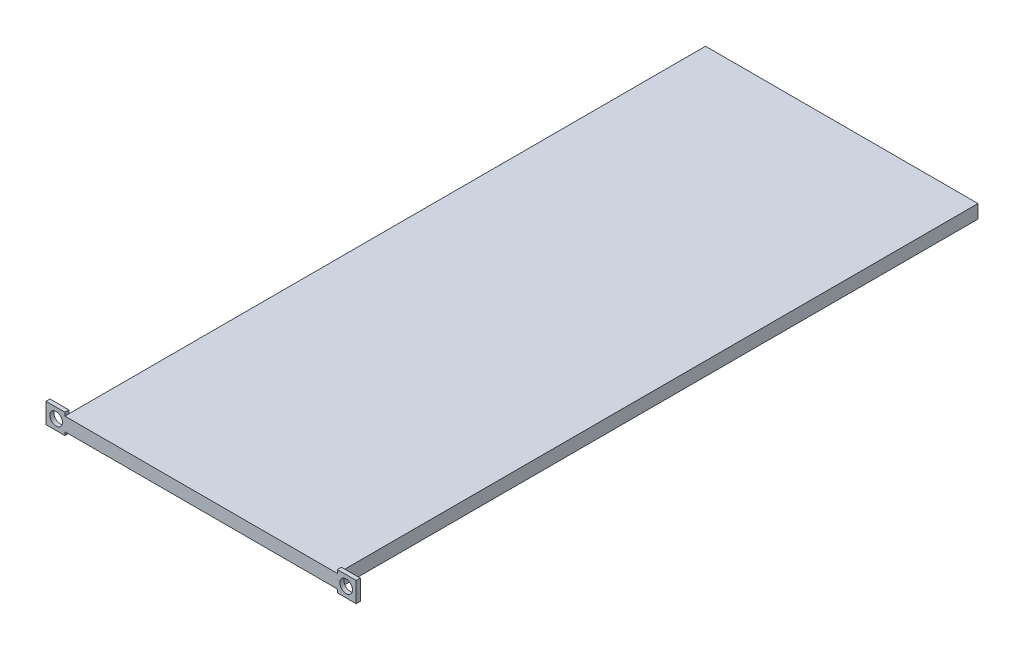
SolidWorks part; units mm, degrees
ref_plane "Front Plane" through (0, 0, 0) normal (0, 0, 1) x (1, 0, 0)
ref_plane "Top Plane" through (0, 0, 0) normal (0, 1, 0) x (1, 0, 0)
ref_plane "Right Plane" through (0, 0, 0) normal (1, 0, 0) x (0, 0, -1)
sketch "Sketch1" plane through (0, 0, 0) normal (0, 0, 1) x (1, 0, 0)
  line L1 (0, 0) -> (202, 0)
  line L2 (0, 0) -> (0, 10)
  line L3 (0, 10) -> (202, 10)
  line L4 (202, 0) -> (202, 10)
  dimension "D1" = 202
  dimension "D2" = 10
extrude "Boss-Extrude1" add sketch "Sketch1" along normal blind 475
sketch "Sketch2" plane through (0, 0, 0) normal (-1, 0, 0) x (0, 0, 1)
  line L0 (475, 10) -> (475, 0) construction
  line L1 (475, 12.5) -> (472, 12.5)
  line L2 (475, 12.5) -> (475, -2.5)
  line L3 (475, -2.5) -> (472, -2.5)
  line L4 (472, 12.5) -> (472, -2.5)
  dimension "D1" = 3
  dimension "D2" = 15
  dimension "D3" = 2.5
extrude "Boss-Extrude2" add sketch "Sketch2" along normal blind 14
sketch "Sketch4" plane through (202, 0, 0) normal (1, 0, 0) x (0, 0, -1)
  line L1 (-475, 12.5) -> (-472, 12.5)
  line L2 (-475, 12.5) -> (-475, -2.5)
  line L3 (-475, -2.5) -> (-472, -2.5)
  line L4 (-472, 12.5) -> (-472, -2.5)
extrude "Boss-Extrude3" add sketch "Sketch4" along normal blind 14
sketch "Sketch3" plane through (0, 0, 472) normal (0, 0, -1) x (-1, 0, 0)
  line L0 (0, 10) -> (0, 0) construction
  line L1 (-101, 36.0752) -> (-101, -22.8304) construction
  circle A0 centre (6.5, 5) radius 4.7
  circle A1 centre (-208.5, 5) radius 4.7
  dimension "D1" = 9.4
  dimension "D2" = 6.5
  dimension "D3" = 5
  dimension "D4" = 101
extrude "Cut-Extrude1" cut sketch "Sketch3" against normal blind 13
